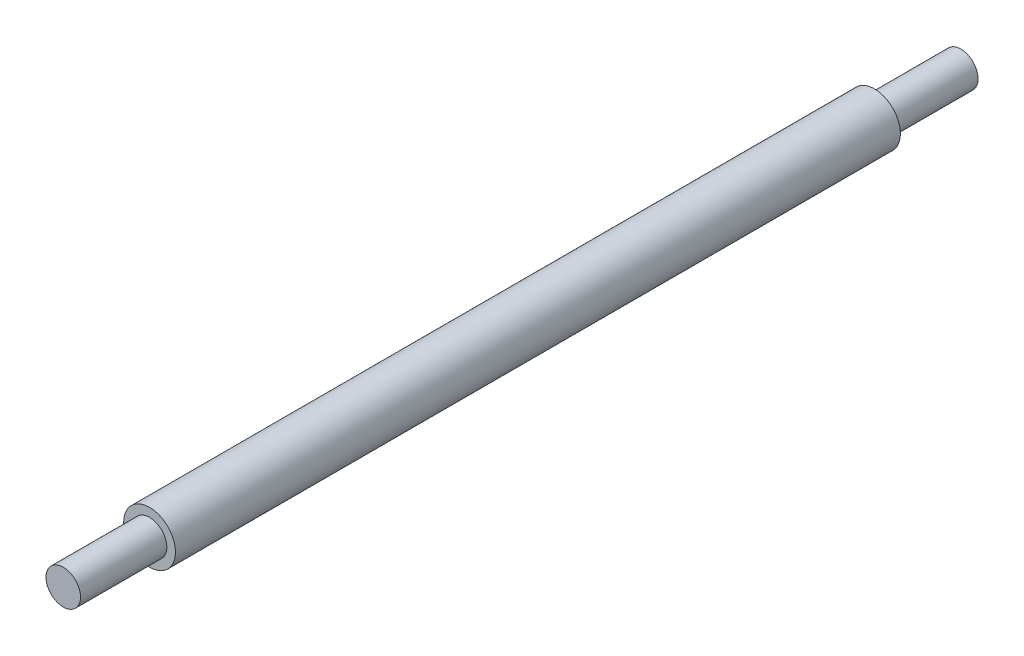
SolidWorks part; units mm, degrees
ref_plane "Front Plane" through (0, 0, 0) normal (0, 0, 1) x (1, 0, 0)
ref_plane "Top Plane" through (0, 0, 0) normal (0, 1, 0) x (1, 0, 0)
ref_plane "Right Plane" through (0, 0, 0) normal (1, 0, 0) x (0, 0, -1)
sketch "Sketch1" plane through (0, 0, 0) normal (0, 0, 1) x (1, 0, 0)
  circle A0 centre (0, 0) radius 3
  circle A1 centre (0, 0) radius 2
  dimension "D1" = 6
  dimension "D2" = 4
extrude "Boss-Extrude1" add sketch "Sketch1" along normal mid plane 84 contours A0
extrude "Boss-Extrude2" add sketch "Sketch1<3>" along normal mid plane 104 contours A1
sketch "Sketch1<3>" plane through (0, 0, 0) normal (0, 0, 1) x (1, 0, 0) same geometry as "Sketch1"
